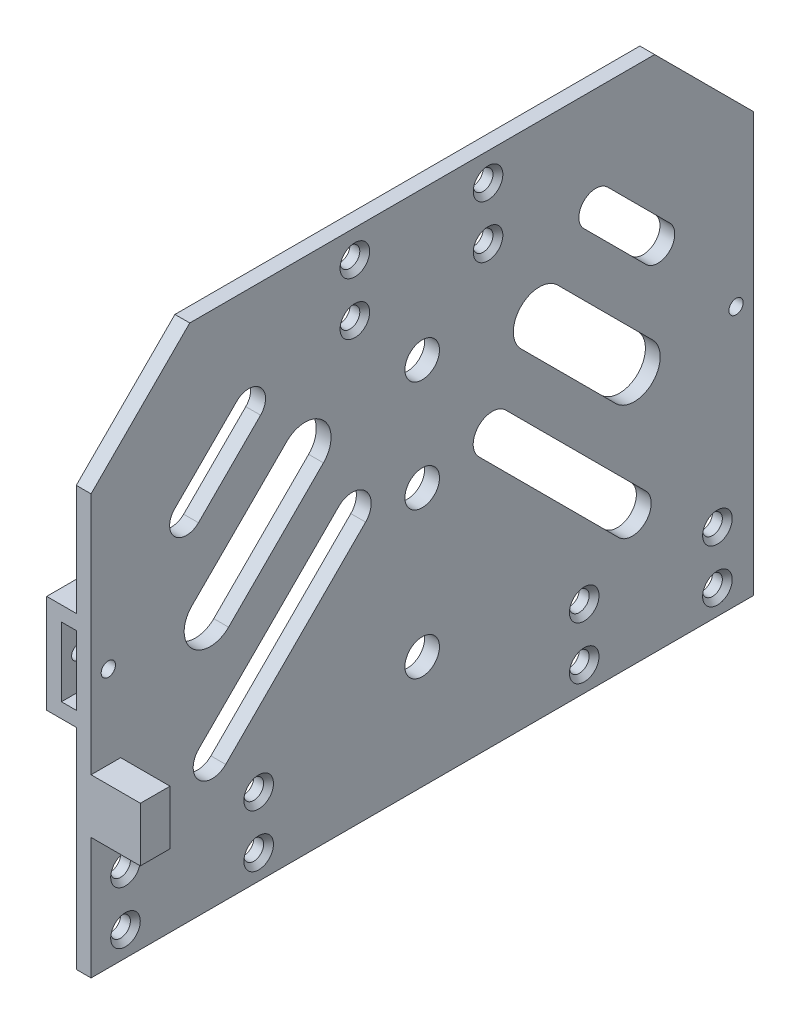
SolidWorks part; units mm, degrees
ref_plane "Спереди" through (0, 0, 0) normal (0, 0, 1) x (1, 0, 0)
ref_plane "Сверху" through (0, 0, 0) normal (0, 1, 0) x (1, 0, 0)
ref_plane "Справа" through (0, 0, 0) normal (1, 0, 0) x (0, 0, -1)
sketch "Эскиз1" plane through (0, 0, 0) normal (1, 0, 0) x (0, 0, -1)
  line L0 (-2, -10.68) -> (-7, -10.68)
  line L1 (122, -10.68) -> (127, -10.68)
  line L18 (0, -15.68) -> (127.2774, -15.68)
  line L19 (127.2774, -15.68) -> (127.2774, 89.32)
  line L20 (127.2774, 89.32) -> (-6.975, 89.32)
  line L21 (-6.975, 89.32) -> (-6.975, -15.68)
  line L22 (-6.975, -15.68) -> (0, -15.68)
  circle A0 centre (0, -10.68) radius 2
  circle A1 centre (27, -10.68) radius 2
  circle A2 centre (27, 0) radius 2
  circle A3 centre (0, 0) radius 2
  circle A4 centre (93, 0) radius 2
  circle A5 centre (93, -10.68) radius 2
  circle A6 centre (120, -10.68) radius 2
  circle A7 centre (120, 0) radius 2
  circle A8 centre (73.5, 73) radius 2
  circle A9 centre (73.5, 83.68) radius 2
  circle A10 centre (46.5, 83.68) radius 2
  circle A11 centre (46.5, 73) radius 2
extrude "Бобышка-Вытянуть1" add sketch "Эскиз1" along normal blind 3 contours A0 L21 L22 L18 L19 L20 A11 A10 A9 A8 A7 A5 A4 A3 A2 A1 A6 region at (0, 36.9743, -60.1529)
sketch "Эскиз2" plane through (3, 0, 0) normal (1, 0, 0) x (0, 0, -1)
  line L0 (-6.975, 9.0038) -> (-0.975, 9.0038)
  line L1 (-0.975, 9.0038) -> (-0.975, 20)
  line L2 (-4.9474, 89.32) -> (-4.9474, -15.68) construction
  line L3 (-0.975, 20) -> (-4.9474, 20)
  line L6 (-4.9474, 20) -> (-6.975, 20)
  line L7 (-6.975, 89.32) -> (-6.975, -15.68) construction
  line L8 (-6.975, 20) -> (-6.975, 9.0038)
  line L9 (-6.975, 9.0038) -> (-4.9474, 9.0038)
extrude "Бобышка-Вытянуть2" add sketch "Эскиз2" along normal blind 10 contours L6 L8 L0 L1 L3 region at (3, 14.5019, 3.975)
sketch "Эскиз9" plane through (3, 0, 0) normal (1, 0, 0) x (0, 0, -1)
  line L0 (12.3732, 55.7809) -> (24.9668, 68.3744) construction
  line L1 (9.9527, 58.2015) -> (22.5462, 70.795)
  line L2 (14.7938, 53.3604) -> (27.3873, 65.9539)
  line L3 (17.1721, 35.7032) -> (36.4041, 54.9352) construction
  line L4 (13.4463, 39.429) -> (32.6783, 58.661)
  line L5 (20.8979, 31.9774) -> (40.1299, 51.2094)
  line L6 (17.5889, 10.9022) -> (45.9489, 39.2622) construction
  line L7 (14.8584, 13.6327) -> (43.2184, 41.9926)
  line L8 (20.3194, 8.1717) -> (48.6794, 36.5317)
  line L9 (60.1512, -15.68) -> (60.1512, 89.32)
  line L10 (-6.975, -15.68) -> (127.2774, -15.68) construction
  line L11 (127.2774, 89.32) -> (-6.975, 89.32) construction
  line L12 (102.7135, 10.9022) -> (74.3536, 39.2622) construction
  line L13 (105.444, 13.6327) -> (77.0841, 41.9926)
  line L14 (99.983, 8.1717) -> (71.6231, 36.5317)
  line L15 (103.1304, 35.7032) -> (83.8983, 54.9352) construction
  line L16 (106.8562, 39.429) -> (87.6241, 58.661)
  line L17 (99.4046, 31.9774) -> (80.1725, 51.2094)
  line L18 (107.9292, 55.7809) -> (95.3357, 68.3744) construction
  line L19 (110.3498, 58.2015) -> (97.7563, 70.795)
  line L20 (105.5086, 53.3604) -> (92.9151, 65.9539)
  line L21 (-6.975, 89.32) -> (13.025, 89.32)
  line L22 (13.025, 89.32) -> (-6.975, 89.32)
  line L23 (-6.975, 89.32) -> (-6.975, 69.32)
  line L24 (-6.975, 89.32) -> (-6.975, 46.82) construction
  line L25 (-6.975, 69.32) -> (13.025, 89.32)
  line L26 (127.2774, 89.32) -> (127.2774, 69.32)
  line L27 (127.2774, 89.32) -> (107.2774, 89.32)
  line L28 (127.2774, 69.32) -> (107.2774, 89.32)
  circle A0 centre (60.1512, 7.1661) radius 3.5
  circle A1 centre (60.1512, 36.82) radius 3.5
  circle A2 centre (60.1512, 59.2809) radius 3.5
  arc A3 (9.9527, 58.2015) -> (14.7938, 53.3604) centre (12.3732, 55.7809) ccw
  arc A4 (27.3873, 65.9539) -> (22.5462, 70.795) centre (24.9668, 68.3744) ccw
  arc A5 (13.4463, 39.429) -> (20.8979, 31.9774) centre (17.1721, 35.7032) ccw
  arc A6 (40.1299, 51.2094) -> (32.6783, 58.661) centre (36.4041, 54.9352) ccw
  arc A7 (14.8584, 13.6327) -> (20.3194, 8.1717) centre (17.5889, 10.9022) ccw
  arc A8 (48.6794, 36.5317) -> (43.2184, 41.9926) centre (45.9489, 39.2622) ccw
  arc A9 (105.444, 13.6327) -> (99.983, 8.1717) centre (102.7135, 10.9022) cw
  arc A10 (71.6231, 36.5317) -> (77.0841, 41.9926) centre (74.3536, 39.2622) cw
  arc A11 (106.8562, 39.429) -> (99.4046, 31.9774) centre (103.1304, 35.7032) cw
  arc A12 (80.1725, 51.2094) -> (87.6241, 58.661) centre (83.8983, 54.9352) cw
  arc A13 (110.3498, 58.2015) -> (105.5086, 53.3604) centre (107.9292, 55.7809) cw
  arc A14 (92.9151, 65.9539) -> (97.7563, 70.795) centre (95.3357, 68.3744) cw
  point P8 (18.67, 62.0777)
  point P15 (26.7881, 45.3192)
  point P20 (31.7689, 25.0822)
  point P38 (88.5336, 25.0822)
  point P45 (93.5144, 45.3192)
  point P52 (101.6325, 62.0777)
  line M24 (127.2774, 46.82) -> (127.2774, 89.32)
  line M25 (127.2774, 89.32) -> (-6.975, 89.32)
  line M26 (-6.975, 89.32) -> (-6.975, 46.82)
extrude "Вырез-Вытянуть3" cut sketch "Эскиз9" against normal blind 4 contours L2 A4 L1 A3 | L5 A6 L4 A5 | L8 A8 L7 A7 | L25 M26 M25 | L9 A2 | L9 A2 | L9 A1 | L9 A1 | L9 A0 | L9 A0 | A10 L14 A9 L13 | A12 L17 A11 L16 | A14 L20 A13 L19 | L28 M24 M25 region at (3, 62.0777, -18.67) region at (3, 45.3192, -26.7881) region at (3, 25.0822, -31.7689) region at (3, 7.1661, -58.6658) region at (3, 82.6533, 0.3083) region at (3, 82.6533, -120.6108) region at (3, 59.2809, -58.6658) region at (3, 59.2809, -61.6367) region at (3, 36.82, -58.6658) region at (3, 36.82, -61.6367) region at (3, 7.1661, -61.6367) region at (3, 25.0822, -88.5336) region at (3, 45.3192, -93.5144) region at (3, 62.0777, -101.6325)
chamfer "Фаска1" distance 1 angle 45 12 edges at (3, -10.68, -122) (3, 0, -122) (3, -10.68, -95) (3, 0, -95) (3, 0, -2) (3, -10.68, -2) (3, -10.68, -29) (3, 0, -29) (3, 73, -48.5) (3, 73, -75.5) (3, 83.68, -75.5) (3, 83.68, -48.5)
sketch "Эскиз10" plane through (0, 0, 0) normal (-1, 0, 0) x (0, 0, 1)
  line L1 (-127.2774, -15.68) -> (-127.2774, 69.32) construction
  line L2 (-127.2774, 36.82) -> (-127.2774, 46.82)
  line L3 (-127.2774, 46.82) -> (-120.2774, 46.82)
  line L4 (-120.2774, 46.82) -> (-120.2774, 26.82)
  line L5 (-120.2774, 26.82) -> (-127.2774, 26.82)
  line L6 (-127.2774, 26.82) -> (-127.2774, 36.82)
  line L8 (-0.025, 26.82) -> (6.975, 26.82)
  line L9 (6.975, 26.82) -> (6.975, 36.82)
  line L10 (6.975, 36.82) -> (6.975, 46.82)
  line L11 (6.975, 46.82) -> (-0.025, 46.82)
  line L12 (-0.025, 46.82) -> (-0.025, 26.82)
extrude "Бобышка-Вытянуть3" add sketch "Эскиз10" along normal blind 6
sketch "Эскиз11" plane through (0, 0, -127.2774) normal (0, 0, -1) x (-1, 0, 0)
  line L0 (0, 46.82) -> (0, 43.82)
  line L1 (0, 26.82) -> (0, 29.82)
  line L2 (0, 29.82) -> (3, 29.82)
  line L3 (3, 29.82) -> (3, 43.82)
  line L4 (3, 43.82) -> (0, 43.82)
  line L5 (0, 29.82) -> (0, 43.82)
extrude "Вырез-Вытянуть4" cut sketch "Эскиз11" against normal through all contours L5 L2 L3 L4 region at (-1.5, 36.82, -127.2774)
sketch "Эскиз12" plane through (-6, 0, 0) normal (-1, 0, 0) x (0, 0, 1)
  line L0 (-127.2774, 36.82) -> (-123.7774, 36.82)
  line L1 (-127.2774, 46.82) -> (-127.2774, 26.82) construction
  line L2 (6.975, 36.82) -> (3.475, 36.82)
  line L3 (6.975, 26.82) -> (6.975, 46.82) construction
  circle A0 centre (-123.7774, 36.82) radius 1.45
  circle A1 centre (3.475, 36.82) radius 1.45
extrude "Вырез-Вытянуть5" cut sketch "Эскиз12" against normal through all contours A0 | A1 region at (-6, 35.411, -123.7774) region at (-6, 36.82, 2.066)
